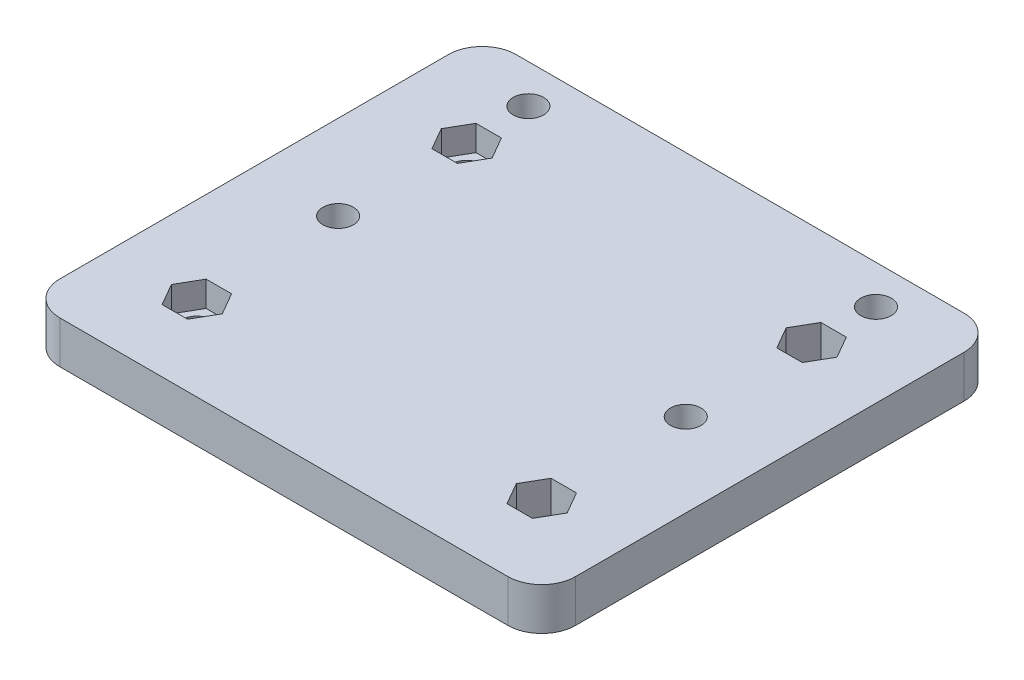
SolidWorks part; units mm, degrees
ref_plane "Front Plane" through (0, 0, 0) normal (0, 0, 1) x (1, 0, 0)
ref_plane "Top Plane" through (0, 0, 0) normal (0, 1, 0) x (1, 0, 0)
ref_plane "Right Plane" through (0, 0, 0) normal (1, 0, 0) x (0, 0, -1)
sketch "Sketch1" plane through (0, 0, 0) normal (0, 1, 0) x (1, 0, 0)
  line L0 (0, 0) -> (101.8, 0) construction
  line L2 (-0.4, 98.26) -> (102.2, 98.26) construction
  line L4 (-25.4, 109.65) -> (126.8, 109.65)
  line L5 (-25.4, 109.65) -> (-25.4, -25)
  line L6 (-25.4, -25) -> (126.8, -25)
  line L7 (126.8, 109.65) -> (126.8, -25)
  line L8 (0, 79.65) -> (101.8, 79.65) construction
  point P0 (0, 0)
  point P1 (0, 79.65)
  point P2 (101.8, 79.65)
  point P3 (101.8, 0)
  point P5 (102.2, 98.26)
  point P6 (-0.4, 42.11)
  point P7 (102.2, 42.11)
  point P9 (-0.4, 98.26)
  point P14 (50.9, 98.26)
  point P22 (50.9, 0)
  dimension "D3" = 18.61
  dimension "D1" = 101.8
  dimension "D2" = 79.65
  dimension "D4" = 102.6
  dimension "D5" = 56.15
  dimension "D6" = 0
  dimension "D7" = 30
  dimension "D8" = 25
  dimension "D9" = 25
  dimension "D10" = 25
extrude "Boss-Extrude1" add sketch "Sketch1" along normal blind 12.5
hole_wizard "M8 Clearance Hole1" positions "Sketch8" profile "Sketch9" hole size "M8" standard "ANSI Metric" end condition through all
sketch "Sketch8" plane through (0, 0, 0) normal (0, -1, 0) x (-1, 0, 0)
  point P0 (-102.2, 42.11)
  point P3 (0.4, 42.11)
  point P6 (0.4, 98.26)
  point P9 (-102.2, 98.26)
sketch "Sketch9" plane through (102.2, 0, -42.11) normal (1, 0, 0) x (0, 0, -1)
  line L0 (0, 0) -> (0, 12.5)
  line L1 (0, 12.5) -> (4.5, 12.5)
  line L2 (4.5, 12.5) -> (4.5, 0)
  line L5 (4.5, 0) -> (0, 0)
  line L11 (0, -6.35) -> (0, 107.95) construction
  dimension "Thru Hole Dia." = 9
  dimension "Thru Hole Depth" = 12.5
hole_wizard "M8 Clearance Hole2" positions "Sketch10" profile "Sketch11" hole size "M8" standard "ANSI Metric" end condition through all
sketch "Sketch10" plane through (0, 0, 0) normal (0, -1, 0) x (-1, 0, 0)
  point P0 (-101.8, 0)
  point P3 (0, 0)
  point P6 (-101.8, 79.65)
  point P9 (0, 79.65)
sketch "Sketch11" plane through (101.8, 0, 0) normal (1, 0, 0) x (0, 0, -1)
  line L0 (0, 0) -> (0, 12.5)
  line L1 (0, 12.5) -> (4.5, 12.5)
  line L2 (4.5, 12.5) -> (4.5, 0)
  line L5 (4.5, 0) -> (0, 0)
  line L11 (0, -6.35) -> (0, 107.95) construction
  dimension "Thru Hole Dia." = 9
  dimension "Thru Hole Depth" = 12.5
fillet "Fillet1" radius 10 4 edges at (-25.4, 6.25, -109.65) (126.8, 6.25, -109.65) (126.8, 6.25, 25) (-25.4, 6.25, 25)
sketch "Sketch12" plane through (0, 12.5, 0) normal (0, 1, 0) x (1, 0, 0)
  line L0 (-25.4, -25) -> (126.8, -25) construction
  line L1 (7.5056, 79.65) -> (3.7528, 86.15)
  line L2 (3.7528, 86.15) -> (-3.7528, 86.15)
  line L3 (-3.7528, 86.15) -> (-7.5056, 79.65)
  line L4 (-7.5056, 79.65) -> (-3.7528, 73.15)
  line L5 (-3.7528, 73.15) -> (3.7528, 73.15)
  line L6 (3.7528, 73.15) -> (7.5056, 79.65)
  line L7 (7.1055, 98.26) -> (3.3528, 104.76)
  line L8 (3.3528, 104.76) -> (-4.1528, 104.76)
  line L9 (-4.1528, 104.76) -> (-7.9056, 98.26)
  line L10 (-7.9056, 98.26) -> (-4.1528, 91.76)
  line L11 (-4.1528, 91.76) -> (3.3528, 91.76)
  line L12 (3.3528, 91.76) -> (7.1055, 98.26)
  line L13 (109.7055, 98.26) -> (105.9528, 104.76)
  line L14 (105.9528, 104.76) -> (98.4472, 104.76)
  line L15 (98.4472, 104.76) -> (94.6944, 98.26)
  line L16 (94.6944, 98.26) -> (98.4472, 91.76)
  line L17 (98.4472, 91.76) -> (105.9528, 91.76)
  line L18 (105.9528, 91.76) -> (109.7055, 98.26)
  line L19 (94.2944, 79.65) -> (98.0472, 73.15)
  line L20 (98.0472, 73.15) -> (105.5528, 73.15)
  line L21 (105.5528, 73.15) -> (109.3056, 79.65)
  line L22 (109.3056, 79.65) -> (105.5528, 86.15)
  line L23 (105.5528, 86.15) -> (98.0472, 86.15)
  line L24 (98.0472, 86.15) -> (94.2944, 79.65)
  line L25 (7.1055, 42.11) -> (3.3528, 48.61)
  line L26 (3.3528, 48.61) -> (-4.1528, 48.61)
  line L27 (-4.1528, 48.61) -> (-7.9056, 42.11)
  line L28 (-7.9056, 42.11) -> (-4.1528, 35.61)
  line L29 (-4.1528, 35.61) -> (3.3528, 35.61)
  line L30 (3.3528, 35.61) -> (7.1055, 42.11)
  line L31 (7.5056, 0) -> (3.7528, 6.5)
  line L32 (3.7528, 6.5) -> (-3.7528, 6.5)
  line L33 (-3.7528, 6.5) -> (-7.5056, 0)
  line L34 (-7.5056, 0) -> (-3.7528, -6.5)
  line L35 (-3.7528, -6.5) -> (3.7528, -6.5)
  line L36 (3.7528, -6.5) -> (7.5056, 0)
  line L37 (94.2944, 0) -> (98.0472, -6.5)
  line L38 (98.0472, -6.5) -> (105.5528, -6.5)
  line L39 (105.5528, -6.5) -> (109.3056, 0)
  line L40 (109.3056, 0) -> (105.5528, 6.5)
  line L41 (105.5528, 6.5) -> (98.0472, 6.5)
  line L42 (98.0472, 6.5) -> (94.2944, 0)
  line L43 (109.7055, 42.11) -> (105.9528, 48.61)
  line L44 (105.9528, 48.61) -> (98.4472, 48.61)
  line L45 (98.4472, 48.61) -> (94.6944, 42.11)
  line L46 (94.6944, 42.11) -> (98.4472, 35.61)
  line L47 (98.4472, 35.61) -> (105.9528, 35.61)
  line L48 (105.9528, 35.61) -> (109.7055, 42.11)
  circle A0 centre (0, 79.65) radius 6.5 construction
  circle A1 centre (-0.4, 98.26) radius 6.5 construction
  circle A2 centre (102.2, 98.26) radius 6.5 construction
  circle A3 centre (101.8, 79.65) radius 6.5 construction
  circle A4 centre (-0.4, 42.11) radius 6.5 construction
  circle A5 centre (0, 0) radius 6.5 construction
  circle A6 centre (101.8, 0) radius 6.5 construction
  circle A7 centre (102.2, 42.11) radius 6.5 construction
  circle A8 centre (102.2, 42.11) radius 4.5 construction
  dimension "D1" = 13
  dimension "D2" = 13
  dimension "D3" = 13
  dimension "D4" = 13
  dimension "D5" = 13
  dimension "D6" = 13
  dimension "D7" = 13
  dimension "D8" = 13
extrude "Cut-Extrude1" cut sketch "Sketch12" against normal offset from surface (10.5 mm away) 2 contours L20 L21 L22 L23 L24 L19 | L42 L37 L38 L39 L40 L41 up to face at (101.8, 0, -4.5)
extrude "Cut-Extrude2" cut sketch "Sketch12<4>" against normal offset from surface (7.5 mm away) 5 contours L5 L6 L1 L2 L3 L4 | L35 L36 L31 L32 L33 L34 up to face at (101.8, 0, -4.5)
sketch "Sketch12<4>" plane through (0, 12.5, 0) normal (0, 1, 0) x (1, 0, 0) same geometry as "Sketch12"
extrude "Cut-Extrude3" cut sketch "Sketch12<5>" along normal blind 6 from surface contours L12 L7 L8 L9 L10 L11 | L15 L16 L17 L18 L13 L14 | L25 L26 L27 L28 L29 L30 | L45 L46 L47 L48 L43 L44 starting at face at (101.8, 0, -4.5)
sketch "Sketch12<5>" plane through (0, 12.5, 0) normal (0, 1, 0) x (1, 0, 0) same geometry as "Sketch12"
